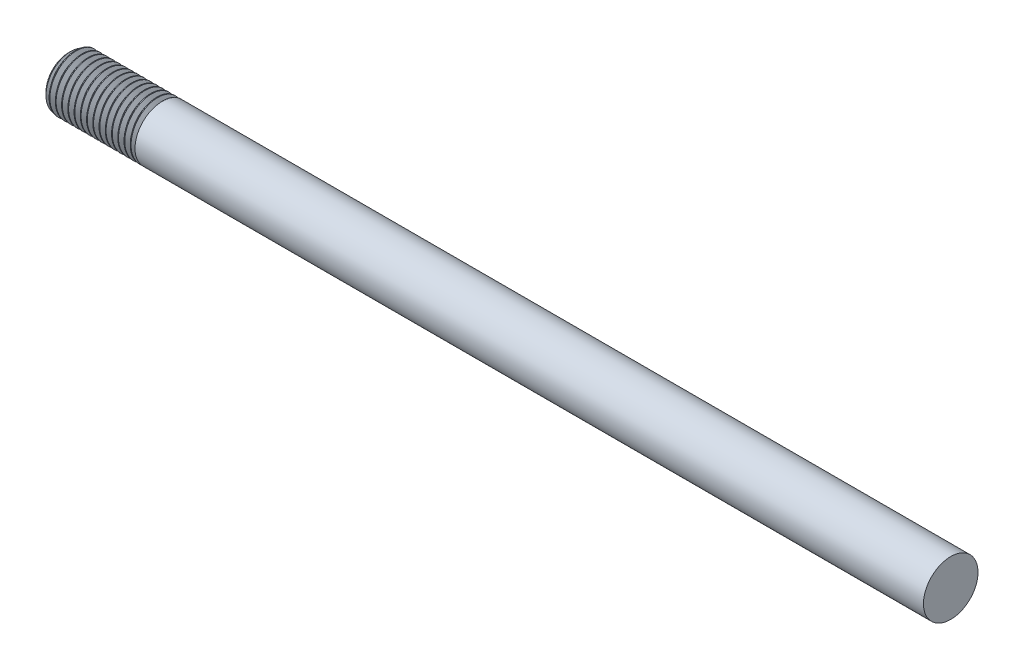
SolidWorks part; units mm, degrees
ref_plane "Front Plane" through (0, 0, 0) normal (0, 0, 1) x (1, 0, 0)
ref_plane "Top Plane" through (0, 0, 0) normal (0, 1, 0) x (1, 0, 0)
ref_plane "Right Plane" through (0, 0, 0) normal (1, 0, 0) x (0, 0, -1)
sketch "Sketch1" plane through (0, 0, 0) normal (0, 0, 1) x (1, 0, 0)
  line L0 (-146.177, 0) -> (146.177, 0) construction
  line L1 (146.177, 9.525) -> (146.177, -9.525) construction
  line L2 (-146.177, 5.5563) -> (-146.177, -5.5562) construction
  line L3 (-127.127, 5.5563) -> (-127.127, -5.5563) construction
  line L4 (-120.777, 4.826) -> (-120.777, -4.826) construction
  line L5 (-104.775, 9.525) -> (-104.775, -9.525) construction
  line L6 (0, 19.812) -> (0, -19.812) construction
  line L7 (123.825, 19.812) -> (123.825, -19.812) construction
  line L8 (146.177, 9.525) -> (123.825, 9.525) construction
  line L9 (146.177, -9.525) -> (123.825, -9.525) construction
  line L10 (-146.177, 0) -> (-298.577, 0) construction
  line L11 (-298.577, 5.5562) -> (-298.577, -5.5562) construction
  line L12 (-279.527, 5.5563) -> (-279.527, -5.5563) construction
  line L13 (-104.775, 9.525) -> (-120.777, 9.525) construction
  line L14 (126.111, 9.525) -> (126.111, -9.525) construction
  line L15 (-116.7765, 0) -> (-108.7755, 0) construction
  circle A0 centre (136.525, 0) radius 4.7625
  circle A1 centre (115.951, 0) radius 5.1435
  circle A2 centre (115.951, 0) radius 5.6578 construction
  circle A3 centre (-89.027, 0) radius 5.6579
  circle A4 centre (-89.027, 0) radius 5.1435
  point P9 (-127.127, 0)
  point P12 (-120.777, 0)
  point P15 (-104.775, 0)
  point P18 (0, 0)
  point P25 (123.825, 0)
  point P33 (-112.776, 9.525)
  point P35 (-112.776, 0)
  point P37 (-116.7765, 0)
  point P39 (-108.7755, 0)
  point P43 (-292.862, -5.5562)
  point P44 (-118.6603, -9.525)
  point P45 (144.0603, -9.525)
  dimension "Port Size" = 10.287
  dimension "Pivot Size" = 9.525
  dimension "D3" = 11.3157
  dimension "Thread Length" = 19.05
  dimension "WF Size" = 9.652
  dimension "Rod Thread" = 11.1125
  dimension "Mount Dia" = 19.05
  dimension "OD" = 39.624
  dimension "Pivot Location" = 9.652
  dimension "Port Location" = 20.574
  dimension "Body End" = 12.7
  dimension "Rear Mount" = 19.05
  dimension "D5" = 19.05
  dimension "D1" = 244.602
  dimension "Mount Shoulder" = 2.286
  dimension "D2" = 8.001
  dimension "Retracted Length" = 292.354
  dimension "D6" = 5.715
  dimension "D4" = 2.1167
  dimension "WF Width" = 6.35
  dimension "Mount Depth" = 16.002
  dimension "D7" = 2.1167
  dimension "Front Port Location" = 38.1
sketch "Sketch2" plane through (0, 0, 0) normal (0, 0, 1) x (1, 0, 0)
  line L1 (-146.177, 5.5563) -> (-127.127, 5.5563)
  line L2 (-146.177, 5.5563) -> (-146.177, 0)
  line L3 (-146.177, 0) -> (-127.127, 0)
  line L4 (-127.127, 5.5563) -> (-127.127, 0)
revolve "Revolve1" add sketch "Sketch2" angle 360 mid plane about L3
chamfer "Chamfer1" distance 0.9525 angle 45 1 edges at (-146.177, 0, 5.5563)
sketch "Sketch3" plane through (-146.177, 0, 0) normal (-1, 0, 0) x (0, 0, 1)
  circle A0 centre (0, 0) radius 5.5563 construction
  circle A1 centre (0, 0) radius 5.5562
curve "Helix/Spiral1" pitch 1.27 height 20.32 radius 5.5562 centre (-146.177, 0, 0) axis (1, 0, 0) start towards (0, 1, 0) parameters "Rod Pitch"=1.27
sketch "Sketch4" plane through (0, 0, 0) normal (0, 0, 1) x (1, 0, 0)
  line L0 (-147.2882, 5.5563) -> (-146.177, 5.5563)
  line L1 (-146.177, 5.5563) -> (-146.6533, 4.7314)
  line L2 (-146.6533, 4.7314) -> (-146.812, 4.7314)
  line L3 (-146.812, 4.7314) -> (-147.2882, 5.5563)
  line L4 (-146.7326, 4.7314) -> (-146.7326, 5.5563) construction
  line L5 (-147.0501, 5.1438) -> (-146.4151, 5.1438) construction
  dimension "D1" = 60
  dimension "D2" = 0.1588
  dimension "D3" = 0.635
sweep "Cut-Sweep1" cut profiles "Sketch4" path "Helix/Spiral1" align with end faces yes
sketch "Sketch18" plane through (0, 0, 0) normal (0, 0, 1) x (1, 0, 0)
  line L0 (33.274, 0) -> (0, 0) construction
  line L1 (-127.127, 0) -> (33.274, 0)
  line L2 (-127.127, 0) -> (-127.127, 5.5499)
  line L3 (-127.127, 5.5499) -> (33.274, 5.5499)
  line L4 (33.274, 0) -> (33.274, 5.5499)
  dimension "D1" = 160.401
  dimension "Rod Diameter" = 11.0998
revolve "Revolve4" add sketch "Sketch18" angle 360 mid plane about L1
equation "\"D5@Sketch1\" = \"Thread Length@Sketch1\""
equation "\"D2@Sketch4\" = \"Rod Pitch@Helix/Spiral1\"*.125"
equation "\"D3@Sketch4\" = \"Rod Pitch@Helix/Spiral1\"*.50"
equation "\"D3@Helix/Spiral1\" = \"Rod Pitch@Helix/Spiral1\"+\"Thread Length@Sketch1\""
equation "\"D1@Chamfer1\" = \"Rod Pitch@Helix/Spiral1\"*.750"
equation "\"D2@Sketch7\" = \"Mount Pitch@Helix/Spiral2\"*.125"
equation "\"D3@Sketch7\" = \"Mount Pitch@Helix/Spiral2\"*.50"
equation "\"D1@Chamfer2\" = \"Mount Pitch@Helix/Spiral2\"*.750"
equation "\"D3@Sketch9\" = \"OD@Sketch1\"*.95"
equation "\"D1@Chamfer3\" = \"D1@Chamfer2\""
equation "\"D3@Helix/Spiral2\" = \"Mount Pitch@Helix/Spiral2\"+\"Mount Depth@Sketch1\""
equation "\"D2@Sketch12\" = \"Pivot Flat@Sketch12\""
equation "\"D1@Boss-Extrude2\" = \"Mount Depth@Sketch1\"/2"
equation "\"D2@Sketch1\" = \"Mount Depth@Sketch1\"/2"
equation "\"D1@Sketch18\" = \"D2@Sketch1\"+\"Stroke Length@Sketch1\""
equation "\"D3@Sketch1\" = \"Port Size@Sketch1\"*1.1"
equation "\"D1@Sketch19\" = \"D3@Sketch1\""
equation "\"D2@Sketch25\" = \"Port Pitch@Helix/Spiral3\"*.125"
equation "\"D3@Sketch25\" = \"Port Pitch@Helix/Spiral3\"*.50"
equation "\"D1@Boss-Extrude5\" = \"Mount Shoulder@Sketch1\""
equation "\"D6@Sketch1\" = \"Rod Pitch@Helix/Spiral1\"*4.5"
equation "\"D7@Sketch1\" = \"Mount Pitch@Helix/Spiral2\"*1.5"
equation "\"D1@Sketch28\" = \"Rear Pitch@Helix/Spiral4\"*.125"
equation "\"D2@Sketch28\" = \"Rear Pitch@Helix/Spiral4\"*.50"
equation "\"D1@Boss-Extrude6\" =\"Mount Depth@Sketch1\"/2"
equation "\"D4@Sketch1\" = \"Rear Pitch@Helix/Spiral4\"*1.5"
equation "\"D3@Helix/Spiral3\" = \"Port Depth@Boss-Extrude4\"+\"Port Pitch@Helix/Spiral3\""
